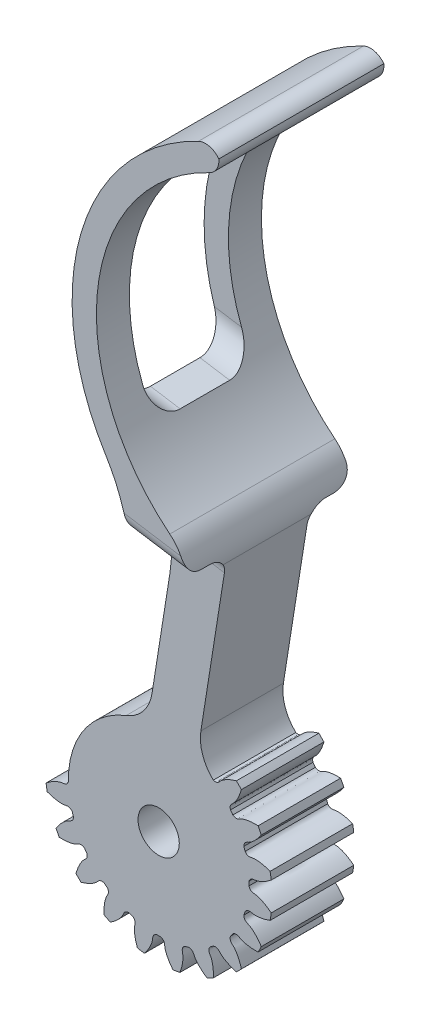
SolidWorks part; units mm, degrees
material "聚脂树脂"
ref_plane "前视基准面" through (0, 0, 0) normal (0, 0, 1) x (1, 0, 0)
ref_plane "上视基准面" through (0, 0, 0) normal (0, 1, 0) x (1, 0, 0)
ref_plane "右视基准面" through (0, 0, 0) normal (1, 0, 0) x (0, 0, -1)
other "Configuration Table"
sketch "草图1" plane through (0, 0, 0) normal (0, 0, 1) x (1, 0, 0)
  circle A0 centre (0, 0) radius 13.75
extrude "凸台-拉伸1" add sketch "草图1" along normal blind 10
ref_axis "基准轴1" through (0, 0, -1.5) along (0, 0, 1)
sketch "草图2" plane through (0, 0, 0) normal (0, 0, 1) x (1, 0, 0)
  line L0 (0, 0) -> (0, 13.75) construction
  circle A0 centre (0, 0) radius 13.75 construction
  arc A1 (0.2416, 10.9348) -> (-0.2416, 10.9348) centre (0, 0) ccw
  arc A2 (3.9764, 15.6228) -> (-3.9764, 15.6228) centre (0, 0) ccw
  spline S0 degree 3 poles (0.2416, 10.9348) (0.764, 11.1168) (0.6964, 11.4839) (0.7661, 11.8375) (0.7736, 11.8719) (0.7829, 11.9108) (0.7941, 11.954) (0.8075, 12.0015) (0.8231, 12.0532) (0.8413, 12.1091) (0.8621, 12.169) (0.8857, 12.2329) (0.9123, 12.3007) (0.9421, 12.3723) (0.9752, 12.4476) (1.0117, 12.5264) (1.0519, 12.6088) (1.0959, 12.6945) (1.1438, 12.7834) (1.1957, 12.8755) (1.2519, 12.9705) (1.3125, 13.0684) (1.3775, 13.1691) (1.4472, 13.2723) (1.5216, 13.3779) (1.601, 13.4858) (1.6853, 13.5958) (1.7747, 13.7078) (1.8694, 13.8216) (1.9693, 13.937) (2.0748, 14.0539) (2.1857, 14.1721) (2.3023, 14.2914) (2.4246, 14.4116) (2.5527, 14.5326) (2.6866, 14.6542) (2.8265, 14.7761) (2.9725, 14.8983) (3.1245, 15.0204) (3.2826, 15.1424) (3.4469, 15.2639) (3.6768, 15.427) (3.8549, 15.5454) (3.9764, 15.6228) knots 0 0 0 0 0.165916 0.170906 0.176664 0.183189 0.190482 0.198542 0.207371 0.216967 0.22733 0.238462 0.250361 0.263027 0.276462 0.290664 0.305634 0.321371 0.337876 0.355149 0.37319 0.391998 0.411574 0.431917 0.453028 0.474907 0.497554 0.520968 0.54515 0.570099 0.595817 0.622302 0.649554 0.677575 0.706363 0.735918 0.766242 0.797333 0.829191 0.861818 0.895212 0.929373 1 1 1 1
  spline S1 degree 3 poles (-0.2416, 10.9348) (-0.764, 11.1168) (-0.6964, 11.4839) (-0.7661, 11.8375) (-0.7736, 11.8719) (-0.7829, 11.9108) (-0.7941, 11.954) (-0.8075, 12.0015) (-0.8231, 12.0532) (-0.8413, 12.1091) (-0.8621, 12.169) (-0.8857, 12.2329) (-0.9123, 12.3007) (-0.9421, 12.3723) (-0.9752, 12.4476) (-1.0117, 12.5264) (-1.0519, 12.6088) (-1.0959, 12.6945) (-1.1438, 12.7834) (-1.1957, 12.8755) (-1.2519, 12.9705) (-1.3125, 13.0684) (-1.3775, 13.1691) (-1.4472, 13.2723) (-1.5216, 13.3779) (-1.601, 13.4858) (-1.6853, 13.5958) (-1.7747, 13.7078) (-1.8694, 13.8216) (-1.9693, 13.937) (-2.0748, 14.0539) (-2.1857, 14.1721) (-2.3023, 14.2914) (-2.4246, 14.4116) (-2.5527, 14.5326) (-2.6866, 14.6542) (-2.8265, 14.7761) (-2.9725, 14.8983) (-3.1245, 15.0204) (-3.2826, 15.1424) (-3.4469, 15.2639) (-3.6768, 15.427) (-3.8549, 15.5454) (-3.9764, 15.6228) knots 0 0 0 0 0.165916 0.170906 0.176664 0.183189 0.190482 0.198542 0.207371 0.216967 0.22733 0.238462 0.250361 0.263027 0.276462 0.290664 0.305634 0.321371 0.337876 0.355149 0.37319 0.391998 0.411574 0.431917 0.453028 0.474907 0.497554 0.520968 0.54515 0.570099 0.595817 0.622302 0.649554 0.677575 0.706363 0.735918 0.766242 0.797333 0.829191 0.861818 0.895212 0.929373 1 1 1 1
extrude "切除-拉伸1" cut sketch "草图2" along normal through all
pattern_circular "阵列(圆周)1" count 20 every 18 about axis through (0, 0, -1.5) along (0, 0, 1) of "切除-拉伸1"
sketch "草图3" plane through (0, 0, 0) normal (0, 0, 1) x (1, 0, 0)
  circle A0 centre (0, 0) radius 12.5 construction
  dimension "Dn" = 25
sketch "草图6" plane through (0, 0, 0) normal (0, 0, -1) x (-1, 0, 0)
  line L0 (0, 0) -> (-10.311, 65.1009) construction
  line L1 (0, 0) -> (38.9643, 6.1713) construction
  line L2 (0, 0) -> (-30.4582, -4.8241) construction
  line L3 (-12.3461, -1.9554) -> (-21.1812, 53.827) construction
  line L4 (2.9631, 0.4693) -> (-2.6968, 36.2041)
  line L5 (-2.9631, -0.4693) -> (-8.6229, 35.2655)
  line L6 (-8.6229, 35.2655) -> (-14.6447, 73.2858)
  line L7 (-14.6447, 73.2858) -> (-21.4537, 55.5478) construction
  line L8 (-14.6447, 73.2858) -> (-7.9754, 90.6601) construction
  line L9 (-14.6447, 73.2858) -> (-11.7977, 80.7025)
  line L10 (-2.9631, -0.4693) -> (2.9631, 0.4693)
  circle A0 centre (0, 0) radius 12.5 construction
  circle A1 centre (-21.4537, 55.5478) radius 24 construction
  circle A2 centre (-21.4537, 55.5478) radius 26.9444 construction
  arc A3 (-11.7977, 80.7025) -> (-2.6968, 36.2041) centre (-21.4537, 55.5478) cw
  arc A4 (-12.8529, 77.9537) -> (-8.6229, 35.2655) centre (-21.4537, 55.5478) cw
  dimension "D1" = 25
  dimension "D4" = 48
  dimension "D5" = 30
  dimension "D2" = 6
  dimension "D3" = 58.22
extrude "凸台-拉伸2" add sketch "草图6" against normal blind 15 and the other way blind 5 contours A3 L9 L6 L5 L10 L4 | L5 | L4 region at (0.1302, 0.8219, 0)
sketch "草图7" plane through (-2.9631, 0.4693, 0) normal (0.9877, -0.1564, 0) x (0, 0, -1)
  line L0 (0, 0) -> (0, 34)
  line L1 (0, 34) -> (5, 34)
  line L3 (5, 34) -> (5, 0)
  line L4 (5, 0) -> (0, 0) construction
  line L5 (5, 0) -> (5, 36.1803) construction
  line L6 (5, 0) -> (0, 0)
  line L7 (-5, 4.6588) -> (-5, 27.3083) construction
  line L8 (-10, 4.6588) -> (0, 4.6588) construction
  line L9 (-15, 34) -> (-15, 0)
  line L10 (-10, 34) -> (-15, 34)
  line L11 (-10, 0) -> (-10, 34)
  line L12 (-15, 0) -> (-10, 0)
  dimension "D1" = 34
extrude "切除-拉伸3" cut sketch "草图7" against normal blind 32 and the other way blind 10
ref_plane "基准面1" through (12.5, 0, 0) normal (1, 0, 0) x (0, 0, -1)
ref_axis "基准轴2" through (0, 0, -6) along (0, 0, 1)
ref_plane "基准面2" through (0, 0, 0) normal (-0.9877, 0.1564, 0) x (0, 0, 1)
ref_plane "基准面3" through (12.3461, -1.9554, 0) normal (-0.9877, 0.1564, 0) x (0, 0, 1)
fillet "圆角2" radius 2 4 edges at (5.3188, 33.5814, 10) (5.3188, 33.5814, 15) (5.3188, 33.5814, 0) (5.3188, 33.5814, -5)
sketch "草图16" plane through (0, 0, 10) normal (0, 0, 1) x (1, 0, 0)
  circle A0 centre (0, 0) radius 2.5
  dimension "D1" = 5
extrude "切除-拉伸5" cut sketch "草图16" against normal blind 16.5
sketch "草图20" plane through (0, 0, 0) normal (0, 0, -1) x (-1, 0, 0)
  line L0 (0, 0) -> (3.6089, 10.325)
  line L1 (3.6089, 10.325) -> (7.1451, 20.4421)
  line L2 (0, 0) -> (10.9348, -0.2416)
  line L3 (10.9348, -0.2416) -> (20.7519, -0.2416)
  circle A0 centre (0, 0) radius 17.5
  circle A1 centre (0, 0) radius 10.9375
  arc A2 (-8.7044, 6.6228) -> (-8.9885, 6.2318) centre (0, 0) ccw construction
  dimension "D1" = 35
extrude "切除-拉伸8" cut sketch "草图20" against normal blind 10 contours A1 L3 A0 L1 region at (-11.1082, 7.7459, 0)
fillet "圆角3" radius 20 1 edges at (2.6968, 36.2041, 5)
fillet "圆角4" radius 5 1 edges at (8.6229, 35.2655, 5)
fillet "圆角5" radius 2 2 edges at (12.8529, 77.9537, 5) (11.7977, 80.7025, 5)
sketch "草图22" plane through (12.3461, -1.9554, 0) normal (-0.9877, 0.1564, 0) x (0, 0, 1)
  line L0 (5, -1.9493) -> (5, 109.7629) construction
  line L1 (10, -1.9493) -> (0, -1.9493) construction
  line L2 (-5, 80.3992) -> (-5, 40.5896) construction
  line L5 (-1, 43.22) -> (11, 43.22)
  line L6 (-1, 43.22) -> (-1, 73.22)
  line L7 (-1, 73.22) -> (11, 73.22)
  line L8 (11, 43.22) -> (11, 73.22)
  line L9 (-1, 43.22) -> (11, 73.22) construction
  line L10 (-1, 73.22) -> (11, 43.22) construction
  point P4 (5, 58.22)
  dimension "D1" = 58.22
  dimension "D2" = 4
  dimension "D3" = 30
extrude "切除-拉伸9" cut sketch "草图22" along normal blind 45
fillet "圆角6" radius 3 4 edges at (-1.1987, 43.9486, 11) (-1.1987, 43.9486, -1) (3.4943, 73.5792, -1) (3.4943, 73.5792, 11)
sketch "草图23" plane through (0, 0, 10) normal (0, 0, 1) x (1, 0, 0)
  line L0 (-1.0432, 12.5907) -> (-1.3177, 10.8578)
  line L1 (1.3394, 27.6338) -> (-1.0432, 12.5907) construction
  line L2 (4.8829, 11.6521) -> (4.6084, 9.9192)
  line L3 (7.969, 31.1367) -> (4.8829, 11.6521) construction
  circle A0 centre (0, 0) radius 10.9375
  arc A1 (-1.7221, 13.6417) -> (-2.5777, 13.5062) centre (0, 0) ccw construction
  arc A2 (-1.7221, 13.6417) -> (-2.5777, 13.5062) centre (0, 0) ccw
  arc A3 (6.6252, 12.0486) -> (5.8534, 12.4419) centre (0, 0) ccw construction
  arc A4 (6.6252, 12.0486) -> (5.8534, 12.4419) centre (0, 0) ccw
  spline S0 degree 3 poles (996.9002, 66.1041) (-88.8946, -5.2942) (-13.4757, 28.9809) (-1.5748, 13.4516) (-1.4488, 13.2768) (-1.314, 13.073) (-1.1971, 12.8801) (-1.1119, 12.7258) (4.1756, 2.4179) (-28.4054, -26.7623) (-988.0977, -147.6932) knots -9.021594 -9.021594 -9.021594 -9.021594 0.502446 0.525093 0.568083 0.608002 0.644851 0.678629 0.694366 6.323146 6.323146 6.323146 6.323146 only from (-1.7221, 13.6417) to (-1.0432, 12.5907) construction
  spline S1 degree 3 poles (-1001.8702, -39.9652) (14.2454, 6.0691) (-2.4742, 7.7001) (-2.931, 11.5081) (-2.9354, 11.558) (-2.9398, 11.6323) (-2.9424, 11.7223) (-2.941, 11.8445) (-2.9339, 11.9853) (-2.9194, 12.1444) (-2.8961, 12.3215) (-2.8626, 12.516) (-2.8175, 12.7274) (-2.7593, 12.9551) (-2.6999, 13.1539) (-2.6447, 13.3205) (3.8605, 31.7266) (86.1798, 22.4348) (-968.5361, -245.1905) knots -1.696649 -1.696649 -1.696649 -1.696649 0.165916 0.170906 0.183189 0.190482 0.207371 0.22733 0.250361 0.276462 0.305634 0.337876 0.37319 0.411574 0.453028 0.474907 0.497554 10.021595 10.021595 10.021595 10.021595 only from (-3.1492, 10.4743) to (-2.5777, 13.5062) construction
  spline S2 degree 3 poles (-1.7221, 13.6417) (-1.653, 13.5549) (-1.5348, 13.399) (-1.3791, 13.1737) (-1.2534, 12.9751) (-1.1451, 12.788) (-1.078, 12.6606) (-1.046, 12.5962) (-1.0432, 12.5907) knots 0.492568 0.492568 0.492568 0.492568 0.546972 0.588426 0.62681 0.662124 0.694366 0.697389 0.697389 0.697389 0.697389
  spline S3 degree 3 poles (-3.1492, 10.4743) (-2.7087, 10.8088) (-2.8864, 11.137) (-2.931, 11.5081) (-2.9354, 11.558) (-2.9398, 11.6323) (-2.9424, 11.7223) (-2.941, 11.8445) (-2.9339, 11.9853) (-2.9194, 12.1444) (-2.8961, 12.3215) (-2.8626, 12.516) (-2.8175, 12.7274) (-2.7593, 12.9551) (-2.6866, 13.1982) (-2.6232, 13.3832) (-2.5848, 13.4873) (-2.5777, 13.5062) knots 0 0 0 0 0.165916 0.170906 0.183189 0.190482 0.207371 0.22733 0.250361 0.276462 0.305634 0.337876 0.37319 0.411574 0.453028 0.497554 0.507432 0.507432 0.507432 0.507432
  spline S4 degree 3 poles (845.3644, -532.484) (-75.0291, 47.9678) (6.1325, 31.3668) (6.6326, 11.8082) (6.6318, 11.5928) (6.6211, 11.3487) (6.6022, 11.1239) (6.5767, 10.9187) (6.5461, 10.7332) (6.5119, 10.5675) (6.4757, 10.4216) (6.4439, 10.3125) (6.4137, 10.2194) (6.3905, 10.1545) (6.3633, 10.0853) (6.3437, 10.0391) (4.7326, 6.5586) (-11.6727, 10.1742) (940.4849, -347.6039) knots -9.021595 -9.021595 -9.021595 -9.021595 0.502446 0.525093 0.568083 0.608002 0.644851 0.678629 0.709336 0.736973 0.761538 0.783033 0.792629 0.809518 0.816811 0.829094 0.834084 2.696649 2.696649 2.696649 2.696649 only from (6.6252, 12.0486) to (6.2318, 8.9885) construction
  spline S5 degree 3 poles (894.1115, -445.8104) (18.7454, -34.2306) (-3.2241, 3.5899) (4.99, 11.7594) (5.1187, 11.8798) (5.2895, 12.0271) (5.4807, 12.1793) (5.6544, 12.3066) (21.7717, 23.3982) (82.9075, -32.5048) (-927.6753, 370.9255) knots -5.323178 -5.323178 -5.323178 -5.323178 0.305634 0.321371 0.355149 0.391998 0.431917 0.474907 0.497554 10.021576 10.021576 10.021576 10.021576 only from (4.8829, 11.6521) to (5.8534, 12.4419) construction
  spline S6 degree 3 poles (6.6252, 12.0486) (6.6301, 11.9377) (6.6341, 11.7422) (6.6276, 11.4683) (6.6126, 11.2338) (6.5902, 11.0188) (6.5619, 10.8235) (6.5293, 10.6479) (6.4939, 10.4921) (6.4623, 10.3749) (6.4317, 10.2737) (6.4078, 10.2024) (6.3839, 10.1378) (6.3633, 10.0853) (6.3437, 10.0391) (6.1867, 9.7) (5.9162, 9.4428) (6.2318, 8.9885) knots 0.492568 0.492568 0.492568 0.492568 0.546972 0.588426 0.62681 0.662124 0.694366 0.723538 0.749639 0.77267 0.783033 0.801458 0.809518 0.816811 0.829094 0.834084 1 1 1 1
  spline S7 degree 3 poles (4.8829, 11.6521) (4.9332, 11.7035) (5.0362, 11.8042) (5.2016, 11.9528) (5.3825, 12.1027) (5.5842, 12.2567) (5.7442, 12.3691) (5.8366, 12.4308) (5.8534, 12.4419) knots 0.302611 0.302611 0.302611 0.302611 0.337876 0.37319 0.411574 0.453028 0.497554 0.507432 0.507432 0.507432 0.507432
extrude "切除-拉伸10" cut sketch "草图23" against normal blind 10 contours S3 A0 L0 S2 A2 | S7 L2 A0 S6 A4 region at (-2.0521, 12.0792, 10) region at (5.6844, 10.8538, 10)
fillet "圆角7" radius 5 2 edges at (4.6084, 9.9192, 5) (-1.3177, 10.8578, 5)
